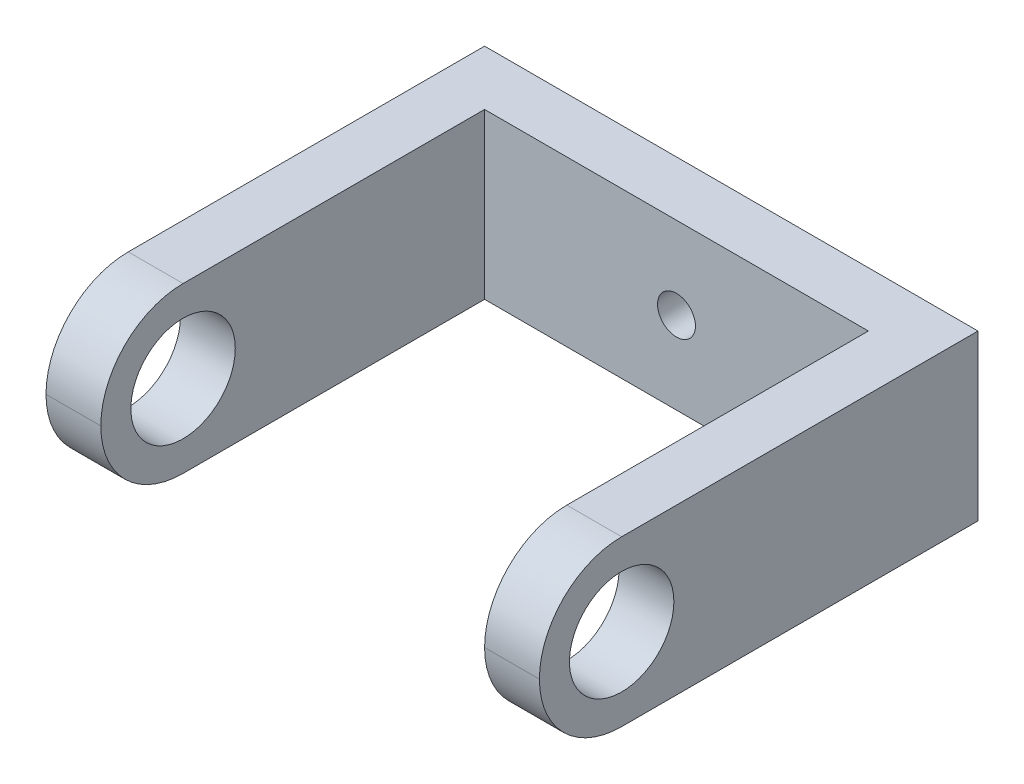
SolidWorks part; units mm, degrees
material "ABS"
ref_plane "Front Plane" through (0, 0, 0) normal (0, 0, 1) x (1, 0, 0)
ref_plane "Top Plane" through (0, 0, 0) normal (0, 1, 0) x (1, 0, 0)
ref_plane "Right Plane" through (0, 0, 0) normal (1, 0, 0) x (0, 0, -1)
sketch "Sketch1" plane through (0, 0, 0) normal (0, 1, 0) x (1, 0, 0)
  line L0 (-17.5, -7.5) -> (-22.5, -7.5)
  line L1 (-22.5, -7.5) -> (-22.5, 32.5)
  line L3 (-22.5, 32.5) -> (22.5, 32.5)
  line L5 (22.5, 32.5) -> (22.5, -7.5)
  line L6 (22.5, -7.5) -> (17.5, -7.5)
  line L7 (17.5, -7.5) -> (17.5, 27.5)
  line L9 (17.5, 27.5) -> (-17.5, 27.5)
  line L11 (-17.5, 27.5) -> (-17.5, -7.5)
  line L16 (0, 27.5) -> (0, 32.5) construction
  point P4 (0, 0)
  point P5 (0, 27.5)
  point P11 (0, 0)
  point P14 (0, 0)
  point P15 (0, 0)
  point P16 (-15, 24.9344)
  point P21 (-15, 21.419)
  dimension "D1" = 5
  dimension "D2" = 35
  dimension "D3" = 27.5
  dimension "D6" = 7.5
extrude "Boss-Extrude1" add sketch "Sketch1" along normal mid plane 15
sketch "Sketch3" plane through (0, 0, 0) normal (1, 0, 0) x (0, 0, -1)
  circle A0 centre (0, 0) radius 4.7625
  dimension "D1" = 9.525
extrude "Cut-Extrude1" cut sketch "Sketch3" against normal through all both and the other way through all
fillet "Fillet1" radius 7.5 4 edges at (20, 7.5, 7.5) (20, -7.5, 7.5) (-20, -7.5, 7.5) (-20, 7.5, 7.5)
hole_wizard "#8-32 Tapped Hole1" positions "Sketch4" profile "Sketch5" tap size "#8-32" standard "ANSI Inch" end condition through all
sketch "Sketch4" plane through (0, 0, -27.5) normal (0, 0, 1) x (1, 0, 0)
  point P0 (0, 0)
sketch "Sketch5" plane through (0, 0, -27.5) normal (1, 0, 0) x (0, -1, 0)
  line L0 (0, 0) -> (0, 5)
  line L1 (0, 5) -> (1.7272, 5)
  line L2 (1.7272, 5) -> (1.7272, 0)
  line L5 (1.7272, 0) -> (0, 0)
  line L11 (0, -6.35) -> (0, 107.95) construction
  dimension "Thru Tap Drill Dia." = 3.4544
  dimension "Thru Tap Drill Depth" = 5
cosmetic thread "Hole Thread1" parameters "D2"=4.1656
